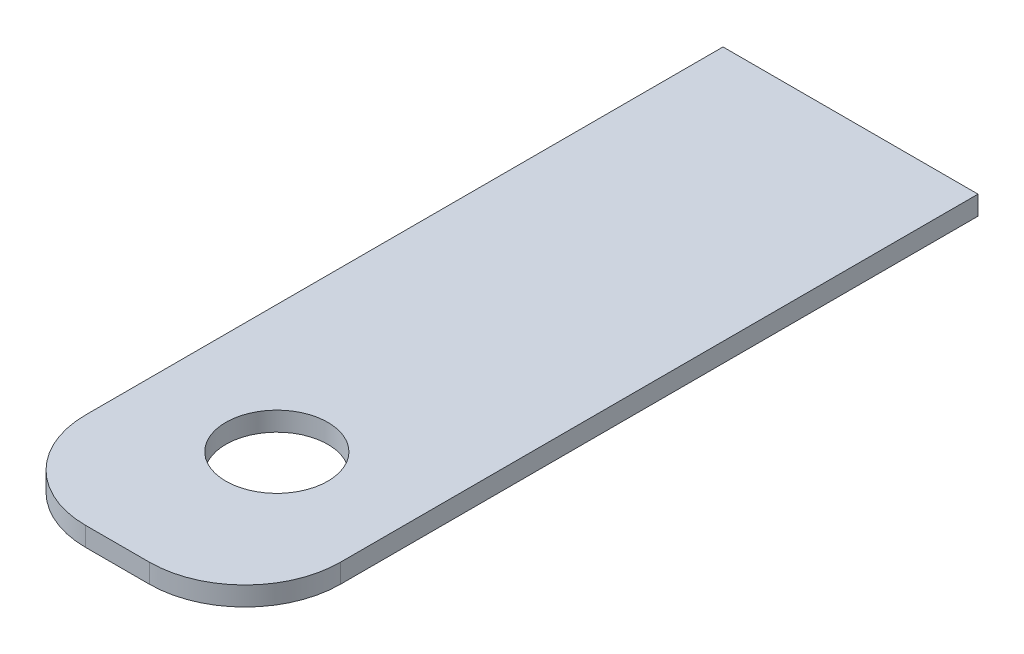
SolidWorks part; units mm, degrees
material "6061-T6 (SS)"
ref_plane "Front Plane" through (0, 0, 0) normal (0, 0, 1) x (1, 0, 0)
ref_plane "Top Plane" through (0, 0, 0) normal (0, 1, 0) x (1, 0, 0)
ref_plane "Right Plane" through (0, 0, 0) normal (1, 0, 0) x (0, 0, -1)
sketch "Sketch1" plane through (0, 0, 0) normal (0, 1, 0) x (1, 0, 0)
  line L1 (0, 0) -> (80, 0)
  line L2 (0, 0) -> (0, -230)
  line L3 (0, -230) -> (80, -230)
  line L4 (80, 0) -> (80, -230)
  dimension "D1" = 80
  dimension "D2" = 230
extrude "Boss-Extrude1" add sketch "Sketch1" along normal blind 6
sketch "Sketch5" plane through (0, 6, 0) normal (0, 1, 0) x (1, 0, 0)
  circle A1 centre (40, -180) radius 20
  point P1 (40, -180)
hole_wizard "Ø32.0 (32) Diameter Hole1" positions "Sketch5" profile "Sketch6" hole size "Ø32.0" standard "DIN" end condition through all
sketch "Sketch6" plane through (40, 6, 180) normal (1, 0, 0) x (0, 0, 1)
  line L0 (0, 0) -> (0, 6)
  line L1 (0, 6) -> (16, 6)
  line L2 (16, 6) -> (16, 0)
  line L5 (16, 0) -> (0, 0)
  line L11 (0, -6.35) -> (0, 107.95) construction
  dimension "Thru Hole Dia." = 32
  dimension "Thru Hole Depth" = 6
fillet "Fillet1" radius 30 2 edges at (0, 3, 230) (80, 3, 230)
